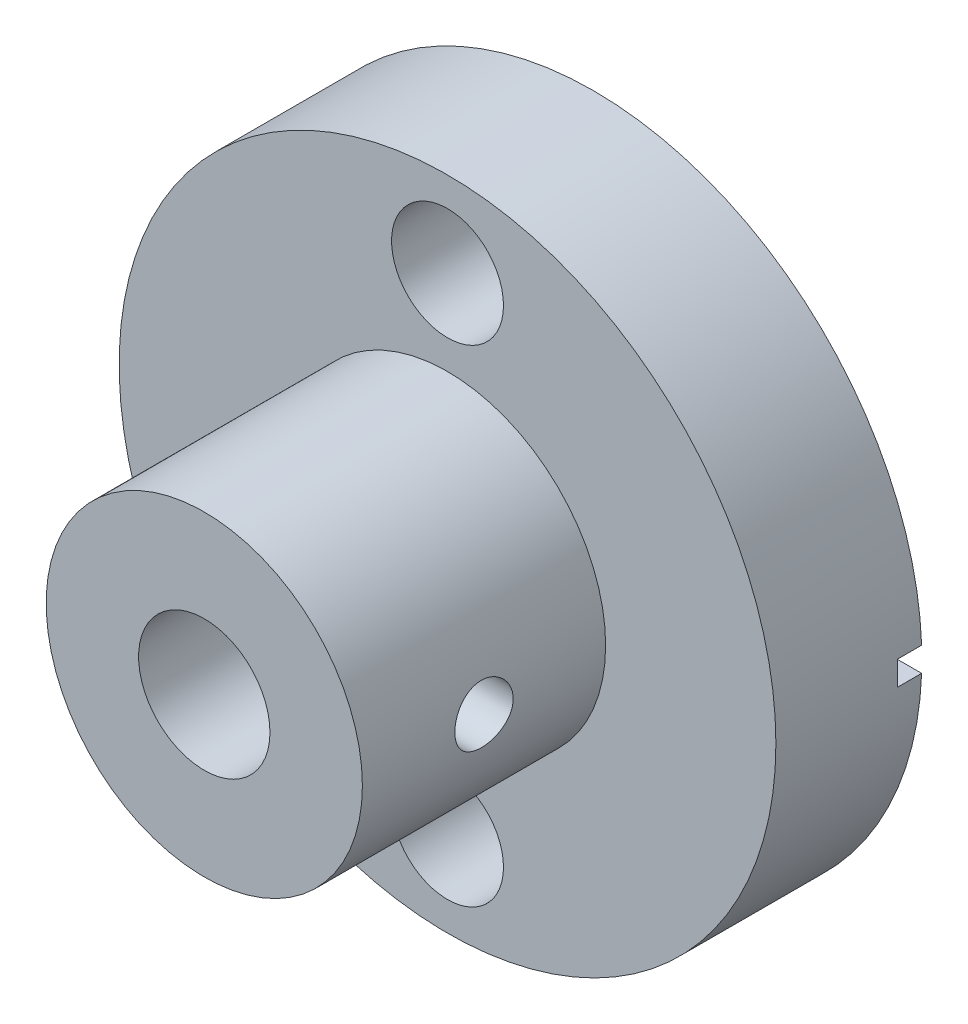
SolidWorks part; units mm, degrees
ref_plane "Front Plane" through (0, 0, 0) normal (0, 0, 1) x (1, 0, 0)
ref_plane "Top Plane" through (0, 0, 0) normal (0, 1, 0) x (1, 0, 0)
ref_plane "Right Plane" through (0, 0, 0) normal (1, 0, 0) x (0, 0, -1)
sketch "Sketch2" plane through (0, 0, 0) normal (0, 0, 1) x (1, 0, 0)
  circle A0 centre (0, 0) radius 13.5
  dimension "D1" = 27
extrude "Boss-Extrude1" add sketch "Sketch2" along normal blind 6
sketch "Sketch3" plane through (0, 0, 6) normal (0, 0, 1) x (1, 0, 0)
  circle A0 centre (0, 0) radius 6.5
  circle A1 centre (0, 0) radius 2.5
  dimension "D1" = 5
  dimension "D2" = 4
extrude "Boss-Extrude2" add sketch "Sketch3" along normal blind 10
sketch "Sketch4" plane through (0, 0, 0) normal (1, 0, 0) x (0, -1, 0)
  line L2 (-13.5, -6) -> (13.5, -6) construction
  circle A0 centre (0, -11) radius 1.2
  dimension "D1" = 2.4
  dimension "D2" = 5
extrude "Cut-Extrude1" cut sketch "Sketch4" against normal blind 25 and the other way blind 25
sketch "Sketch5" plane through (0, 0, 6) normal (0, 0, 1) x (1, 0, 0)
  circle A0 centre (0, 10) radius 2.3
  circle A1 centre (0, 0) radius 13.5 construction
  dimension "D1" = 4.6
  dimension "D2" = 10
ref_axis "Axis1" through (0, 0, -0.8) along (0, 0, 1)
sketch "Sketch6" plane through (0, 0, 6) normal (0, 0, 1) x (1, 0, 0)
  circle A0 centre (0, 0) radius 2.7
  dimension "D1" = 5.4
extrude "Cut-Extrude3" cut sketch "Sketch6" against normal blind 20 and the other way blind 50
extrude "Cut-Extrude4" cut sketch "Sketch5" against normal blind 10
mirror "Mirror1" about plane through (0, 0, 0) normal (0, 1, 0) of "Cut-Extrude4"
sketch "Sketch7" plane through (0, 0, 6) normal (0, 0, 1) x (1, 0, 0)
  circle A0 centre (0, 10) radius 3.175
  dimension "D1" = 6.35
sketch "Sketch8" plane through (0, 0, 0) normal (0, 0, -1) x (-1, 0, 0)
  line L1 (-18.5, 0.5) -> (-8.5, 0.5)
  line L2 (-18.5, 0.5) -> (-18.5, -0.5)
  line L3 (-18.5, -0.5) -> (-8.5, -0.5)
  line L4 (-8.5, 0.5) -> (-8.5, -0.5)
  line L5 (-18.5, 0.5) -> (-8.5, -0.5) construction
  line L6 (-18.5, -0.5) -> (-8.5, 0.5) construction
  circle A0 centre (0, 0) radius 13.5 construction
  point P0 (-13.5, 0)
  dimension "D1" = 1
  dimension "D2" = 10
extrude "Cut-Extrude5" cut sketch "Sketch8" against normal blind 1
mirror "Mirror2" about plane through (0, 0, 0) normal (1, 0, 0) of "Cut-Extrude5"
